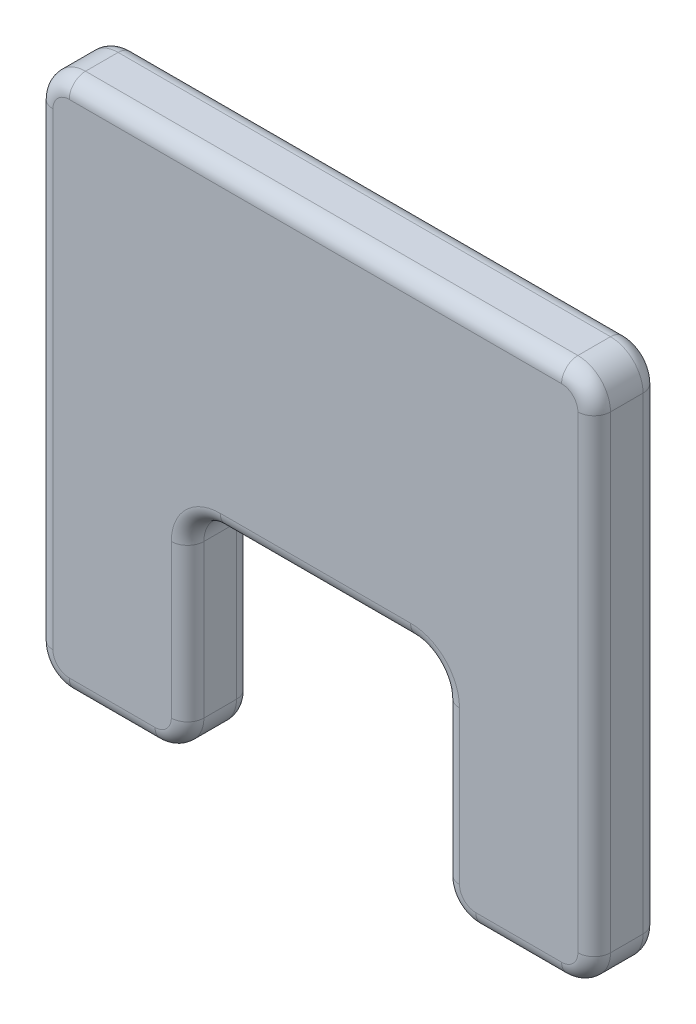
SolidWorks part; units mm, degrees
material "Polyurethane Foam Flexible"
ref_plane "Front Plane" through (0, 0, 0) normal (0, 0, 1) x (1, 0, 0)
ref_plane "Top Plane" through (0, 0, 0) normal (0, 1, 0) x (1, 0, 0)
ref_plane "Right Plane" through (0, 0, 0) normal (1, 0, 0) x (0, 0, -1)
sketch "Sketch1" plane through (0, 0, 0) normal (0, 0, 1) x (1, 0, 0)
  line L0 (-93.2955, 250.6666) -> (-93.2955, -223.9129) construction
  line L1 (-93.2955, 185.6621) -> (341.3045, 185.6621)
  line L2 (-93.2955, 185.6621) -> (-93.2955, -230.2629)
  line L3 (-93.2955, -230.2629) -> (24.3822, -230.2629)
  line L4 (341.3045, 185.6621) -> (341.3045, -230.2629)
  line L5 (223.6267, -230.2629) -> (341.3045, -230.2629)
  line L7 (24.3822, -230.2629) -> (24.3822, -60.2629)
  line L8 (24.3822, -60.2629) -> (223.6267, -60.2629)
  line L9 (223.6267, -230.2629) -> (223.6267, -60.2629)
  line L10 (24.3822, -223.9129) -> (24.3822, -60.2629) construction
  line L11 (16.7045, -230.2629) -> (-93.2955, -230.2629) construction
  line L12 (341.3045, -223.9129) -> (341.3045, 250.6666) construction
  point P13 (0, 0)
  point P14 (-93.2955, 189.7011)
  point P15 (0, 0)
  point P16 (0, 0)
  point P17 (0, 0)
  point P18 (0, 0)
  point P19 (0, 0)
  dimension "D1" = 415.925
extrude "Boss-Extrude1" add sketch "Sketch1" along normal blind 50.8
fillet "Fillet1" radius 25.4 8 edges at (24.3822, -230.2629, 25.4) (-93.2955, -230.2629, 25.4) (-93.2955, 185.6621, 25.4) (341.3045, 185.6621, 25.4) (341.3045, -230.2629, 25.4) (223.6267, -230.2629, 25.4) (223.6267, -60.2629, 25.4) (24.3822, -60.2629, 25.4)
fillet "Fillet2" radius 12.7 32 edges at (31.8217, -67.7023, 0) (124.0045, -60.2629, 0) (216.1872, -67.7023, 0) (223.6267, -145.2629, 0) (231.0662, -222.8234, 0) (282.4656, -230.2629, 0) (333.865, -222.8234, 0) (341.3045, -22.3004, 0) (333.865, 178.2227, 0) (124.0045, 185.6621, 0) (-85.856, 178.2227, 0) (-93.2955, -22.3004, 0) (-85.856, -222.8234, 0) (-34.4566, -230.2629, 0) (16.9428, -222.8234, 0) (24.3822, -145.2629, 0) (-85.856, -222.8234, 50.8) (-93.2955, -22.3004, 50.8) (-85.856, 178.2227, 50.8) (124.0045, 185.6621, 50.8) (333.865, 178.2227, 50.8) (341.3045, -22.3004, 50.8) (333.865, -222.8234, 50.8) (282.4656, -230.2629, 50.8) (231.0662, -222.8234, 50.8) (223.6267, -145.2629, 50.8) (216.1872, -67.7023, 50.8) (124.0045, -60.2629, 50.8) (31.8217, -67.7023, 50.8) (24.3822, -145.2629, 50.8) (16.9428, -222.8234, 50.8) (-34.4566, -230.2629, 50.8)
